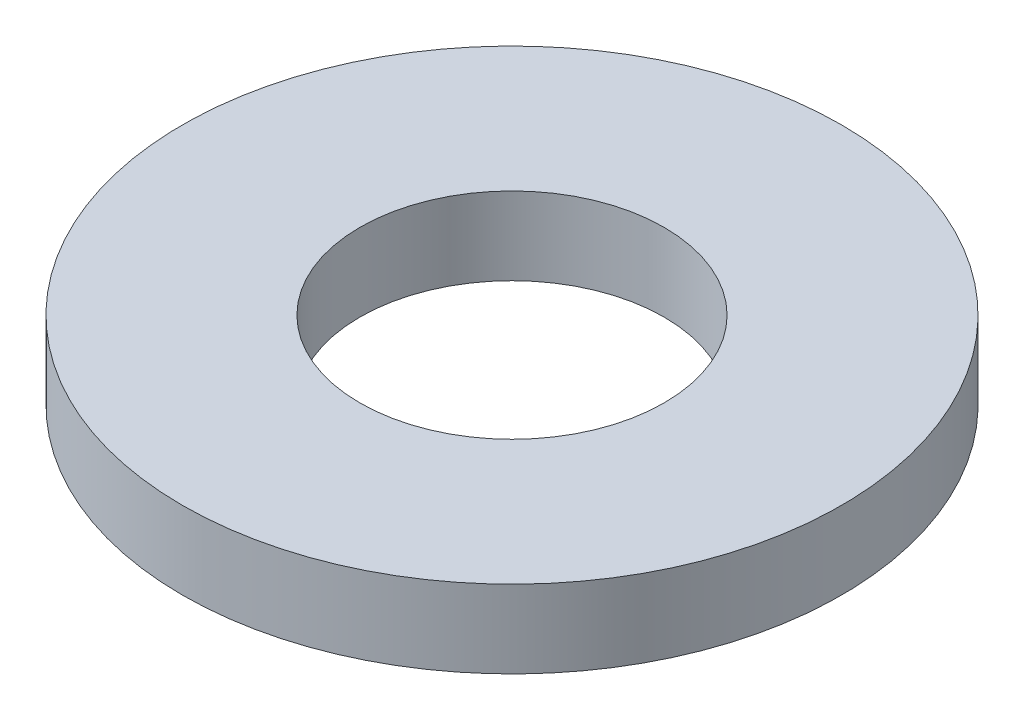
SolidWorks part; units mm, degrees
ref_plane "Front Plane" through (0, 0, 0) normal (0, 0, 1) x (1, 0, 0)
ref_plane "Top Plane" through (0, 0, 0) normal (0, 1, 0) x (1, 0, 0)
ref_plane "Right Plane" through (0, 0, 0) normal (1, 0, 0) x (0, 0, -1)
sketch "Sketch1" plane through (0, 0, 0) normal (0, 1, 0) x (1, 0, 0)
  circle A0 centre (0, 0) radius 97.5
  dimension "FLANGE_OD" = 195
extrude "Boss-Extrude1" add sketch "Sketch1" along normal blind 23
sketch "Sketch2" plane through (0, 0, 0) normal (0, 1, 0) x (1, 0, 0)
  circle A0 centre (0, 0) radius 45
  dimension "BORE_D" = 90
extrude "Cut-Extrude1" cut sketch "Sketch2" along normal through all
sketch "Sketch3" plane through (0, 23, 0) normal (0, 1, 0) x (1, 0, 0)
  circle A0 centre (0, 0) radius 31.0477 construction
  circle A1 centre (-31.0477, 0) radius 6.7253
  dimension "BOLT_D" = 13.4506
  dimension "BOLT_PCD" = 62.0954
extrude "Cut-Extrude2" cut sketch "Sketch3" against normal blind 21.2638 rebuild error yes
pattern_circular "CirPattern1" count 6 over 360 rebuild error yes
